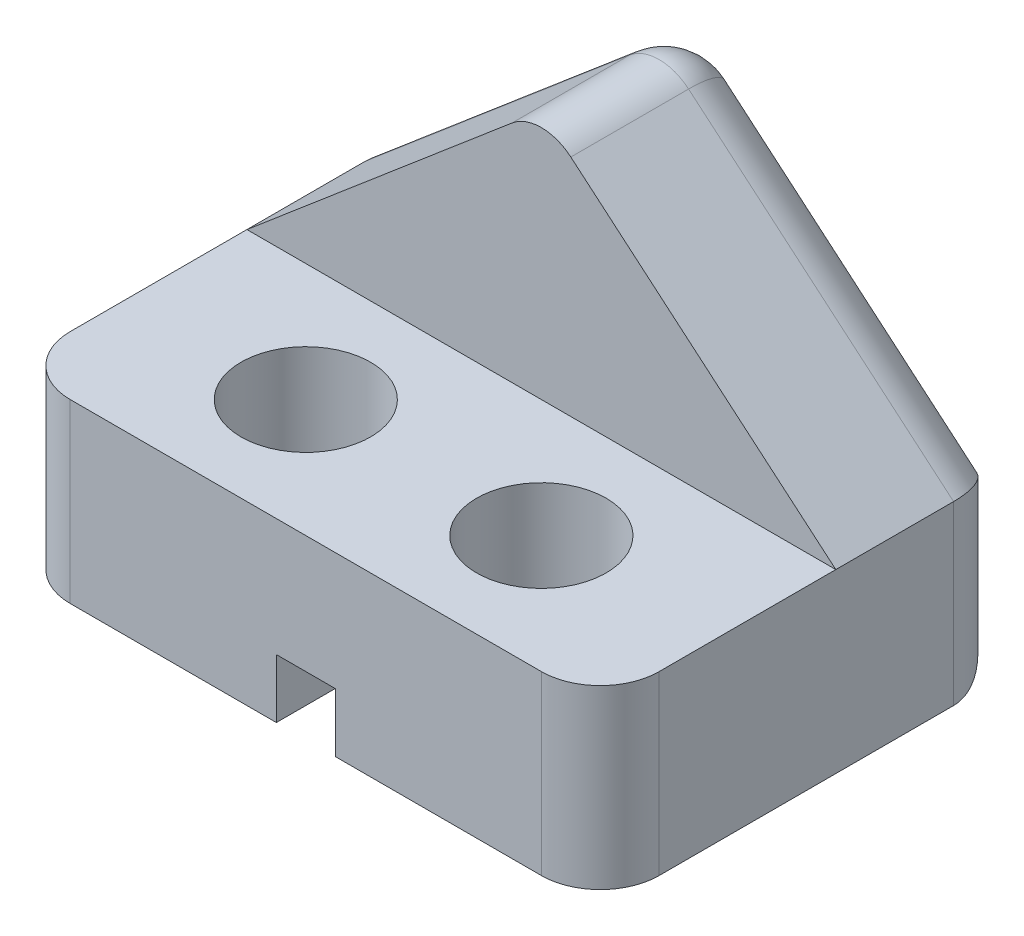
SolidWorks part; units mm, degrees
material "光敏树脂"
ref_plane "前视基准面" through (0, 0, 0) normal (0, 0, 1) x (1, 0, 0)
ref_plane "上视基准面" through (0, 0, 0) normal (0, 1, 0) x (1, 0, 0)
ref_plane "右视基准面" through (0, 0, 0) normal (1, 0, 0) x (0, 0, -1)
sketch "草图4" plane through (0, 0, 0) normal (0, 1, 0) x (1, 0, 0)
  line L0 (0, 19.066) -> (0, -21.6542) construction
  line L1 (-34.6812, 0) -> (36.234, 0) construction
  line L3 (-5, 2) -> (5, 2)
  line L4 (-5, 2) -> (-5, -2)
  line L5 (-5, -2) -> (5, -2)
  line L6 (5, 2) -> (5, -2)
  line L7 (-5, 2) -> (5, -2) construction
  line L8 (-5, -2) -> (5, 2) construction
  circle A0 centre (-2, 0) radius 1.1
  circle A1 centre (2, 0) radius 1.1
  point P9 (0, 0)
  dimension "D1" = 2.2
  dimension "D2" = 4
  dimension "D3" = 10
  dimension "D4" = 4
extrude "凸台-拉伸2" add sketch "草图4" along normal blind 3
sketch "草图5" plane through (0, 0, -2) normal (0, 0, -1) x (-1, 0, 0)
  line L0 (0, -1.3488) -> (0, 11.0944) construction
  line L1 (5, 0) -> (-5, 0)
  line L2 (-5, 0) -> (-5, 3)
  line L3 (-5, 3) -> (-0.5, 6.8165)
  line L4 (5, 0) -> (5, 3)
  line L5 (5, 3) -> (0.5, 6.8165)
  arc A0 (-0.5, 6.8165) -> (0.5, 6.8165) centre (0, 6.227) cw
  point P10 (0, 0)
  point P13 (0, 7.2406)
  point P14 (0, 7)
  dimension "D1" = 1
  dimension "D2" = 7
extrude "凸台-拉伸3" add sketch "草图5" along normal blind 3
sketch "草图6" plane through (0, 0, -5) normal (0, 0, -1) x (-1, 0, 0)
  line L0 (0, -1.2256) -> (0, 9.3075) construction
  line L1 (-5, 0) -> (5, 0) construction
  line L2 (-0.5, 1) -> (0.5, 1)
  line L3 (-0.5, 1) -> (-0.5, 0)
  line L4 (-0.5, 0) -> (0.5, 0)
  line L5 (0.5, 1) -> (0.5, 0)
  line L6 (-0.5, 1) -> (0.5, 0) construction
  line L7 (-0.5, 0) -> (0.5, 1) construction
  point P3 (0, 0.5)
  dimension "D1" = 1
  dimension "D2" = 1
extrude "切除-拉伸3" cut sketch "草图6" against normal through all
fillet "圆角1" radius 1 12 edges at (0.5, 0.5, -5) (2.75, 0, -5) (5, 1.5, -5) (2.75, 4.9083, -5) (0, 7, -5) (-2.75, 4.9083, -5) (-5, 1.5, -5) (-2.75, 0, -5) (-0.5, 0.5, -5) (0, 1, -5) (5, 1.5, 2) (-5, 1.5, 2)
